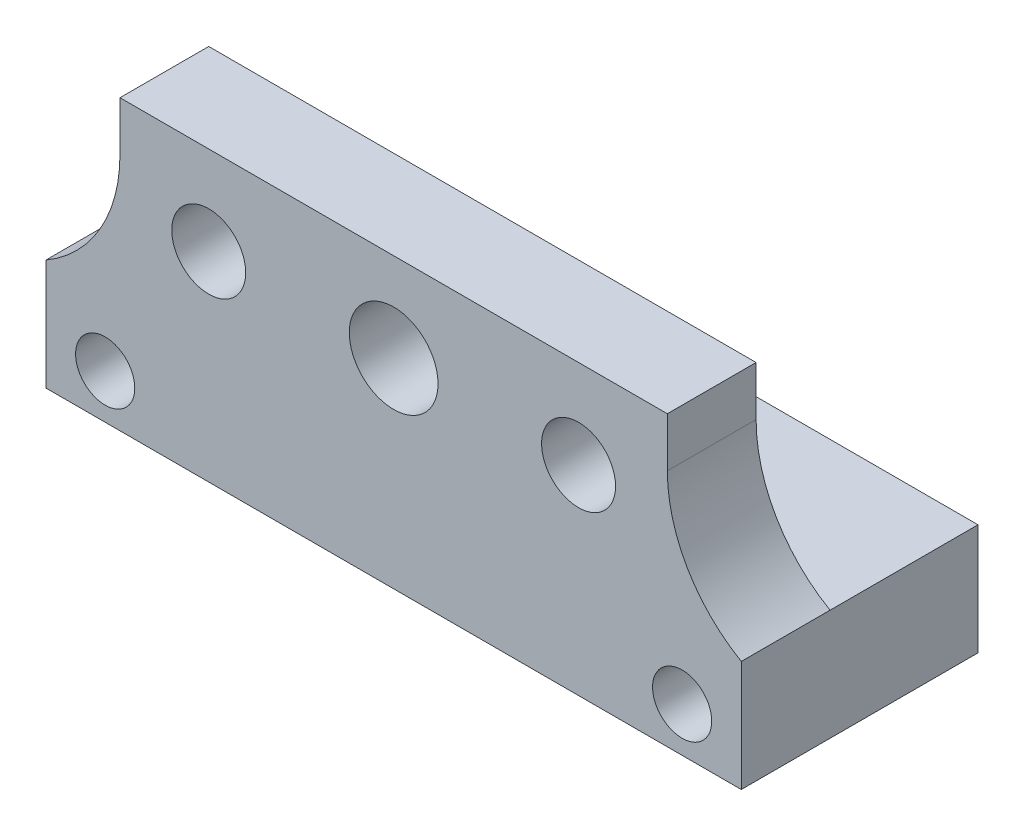
SolidWorks part; units mm, degrees
material "Polyetheretherketone (PEEK)"
ref_plane "Front Plane" through (0, 0, 0) normal (0, 0, 1) x (1, 0, 0)
ref_plane "Top Plane" through (0, 0, 0) normal (0, 1, 0) x (1, 0, 0)
ref_plane "Right Plane" through (0, 0, 0) normal (1, 0, 0) x (0, 0, -1)
ref_plane "Plane1" through (0, 0, 1.2) normal (0, 0, 1) x (1, 0, 0)
sketch "Sketch1" plane through (0, 0, 1.2) normal (0, 0, 1) x (1, 0, 0)
  line L0 (7.4, 2.4) -> (0, 2.4)
  line L1 (0, 2.4) -> (0, 0)
  line L2 (0, 0) -> (7.4, 0)
  line L3 (7.4, 0) -> (7.4, 2.4)
  line L5 (-1, 0) -> (8.4, 0)
  line L6 (-1, 0) -> (-1, -1.5)
  line L7 (-1, -1.5) -> (8.4, -1.5)
  line L8 (8.4, 0) -> (8.4, -1.5)
  point P8 (3.7, 0)
  point P9 (3.7, 0)
  dimension "D1" = 1.5
  dimension "D2" = 9.4
  dimension "D3" = 7.4
  dimension "D4" = 2.4
extrude "Boss-Extrude1" add sketch "Sketch1" against normal blind 1.2 contours L2 L3 L0 L1 | L8 L5 L2 L6 L7 region at (3.7, 1.2, 1.2) region at (3.7, -0.75, 1.2)
hole_wizard "Hole1" positions "Sketch8" profile "Sketch7" legacy end condition through all
sketch "Sketch8" plane through (0, 0, 1.2) normal (0, 0, 1) x (1, 0, 0)
  point P0 (6.2, 1.2)
  point P2 (1.2, 1.2)
  dimension "D1" = 1.2
  dimension "D2" = 1.2
  dimension "D3" = 5
sketch "Sketch7" plane through (6.2, 1.2, 1.2) normal (1, 0, 0) x (0, -1, 0)
  line L0 (0, 0) -> (0, 1.3803)
  line L1 (0, 1.3803) -> (0.3, 1.2)
  line L2 (0.3, 1.2) -> (0.3, 0.9)
  line L3 (0.3, 0.9) -> (0.5, 0.9)
  line L4 (0.5, 0) -> (0, 0)
  line L5 (0, -11.3109) -> (0, 121.1557) construction
  line L6 (0, 1.3803) -> (-0.3, 1.2) construction
  line L7 (0.5, 0.9) -> (0.5, 0)
  dimension "Depth" = 1.2
  dimension "Drill Angle" = 118
  dimension "Diameter" = 0.6
  dimension "C-Bore Diameter" = 1
  dimension "C-Bore Depth" = 0.9
sketch "Sketch11" plane through (0, 0, 0) normal (0, 0, -1) x (-1, 0, 0)
  line L1 (-8.4, 0) -> (1, 0)
  line L2 (-8.4, 0) -> (-8.4, -1.5)
  line L3 (-8.4, -1.5) -> (1, -1.5)
  line L4 (1, 0) -> (1, -1.5)
  dimension "D1" = 9.4
extrude "Boss-Extrude5" add sketch "Sketch11" along normal blind 2
fillet "Fillet1" radius 2 2 edges
hole_wizard "Ø0.8 (0.8) Diameter Hole1" positions "Sketch17" profile "Sketch16" hole size "Ø0.8" standard "ISO" end condition through all
sketch "Sketch17" plane through (0, 0, 1.2) normal (0, 0, 1) x (1, 0, 0)
  line L0 (-1, 0) -> (-1, -1.5) construction
  line L2 (8.4, -1.5) -> (-1, -1.5) construction
  point P0 (-0.2, -0.9)
  point P2 (7.6, -0.9)
  dimension "D1" = 7.8
  dimension "D2" = 0.8
  dimension "D3" = 0.6
sketch "Sketch16" plane through (-0.2, -0.9, 1.2) normal (1, 0, 0) x (0, -1, 0)
  line L0 (0, 0) -> (0, 3.2)
  line L1 (0, 3.2) -> (0.4, 3.2)
  line L2 (0.4, 3.2) -> (0.4, 0)
  line L5 (0.4, 0) -> (0, 0)
  line L11 (0, -6.35) -> (0, 107.95) construction
  dimension "Thru Hole Dia." = 0.8
  dimension "Thru Hole Depth" = 3.2
hole_wizard "M1.0 Clearance Hole1" positions "Sketch18" profile "Sketch19" hole size "M1.0" standard "ANSI Metric" end condition up to next
sketch "Sketch18" plane through (0, 0, 1.2) normal (0, 0, 1) x (1, 0, 0)
  line L0 (6.2, 1.2) -> (1.2, 1.2) construction
  circle A0 centre (6.2, 1.2) radius 0.3 construction
  circle A1 centre (6.2, 1.2) radius 0.3
  circle A2 centre (1.2, 1.2) radius 0.3 construction
  circle A3 centre (1.2, 1.2) radius 0.3
  point P13 (3.7, 1.2)
sketch "Sketch19" plane through (3.7, 1.2, 1.2) normal (1, 0, 0) x (0, -1, 0)
  line L0 (0, 0) -> (0, 1.2)
  line L1 (0, 1.2) -> (0.6, 1.2)
  line L2 (0.6, 1.2) -> (0.6, 0)
  line L5 (0.6, 0) -> (0, 0)
  line L11 (0, -6.35) -> (0, 107.95) construction
  dimension "Thru Hole Dia." = 1.2
  dimension "Thru Hole Depth" = 1.2
